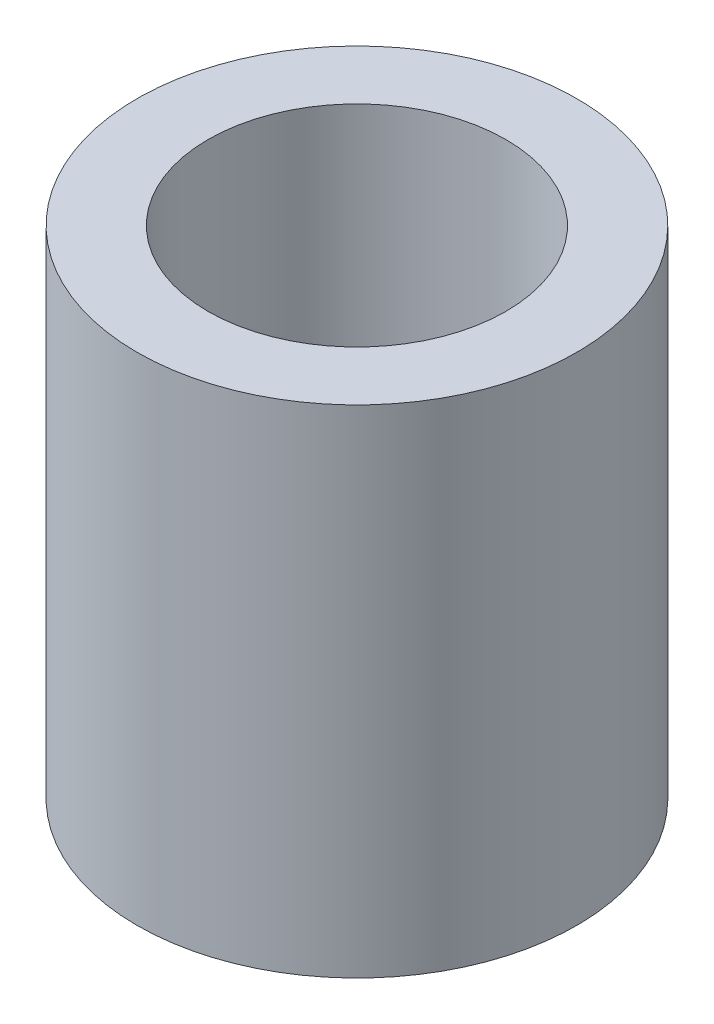
SolidWorks part; units mm, degrees
ref_plane "Front Plane" through (0, 0, 0) normal (0, 0, 1) x (1, 0, 0)
ref_plane "Top Plane" through (0, 0, 0) normal (0, 1, 0) x (1, 0, 0)
ref_plane "Right Plane" through (0, 0, 0) normal (1, 0, 0) x (0, 0, -1)
sketch "Sketch1" plane through (0, 0, 0) normal (0, 1, 0) x (1, 0, 0)
  circle A0 centre (0, 0) radius 3.1
  dimension "D1" = 6.2
extrude "Boss-Extrude1" add sketch "Sketch1" along normal blind 7
sketch "Sketch2" plane through (0, 7, 0) normal (0, 1, 0) x (1, 0, 0)
  circle A0 centre (0, 0) radius 2.1
  dimension "D1" = 4.2
extrude "Cut-Extrude1" cut sketch "Sketch2" against normal blind 7
